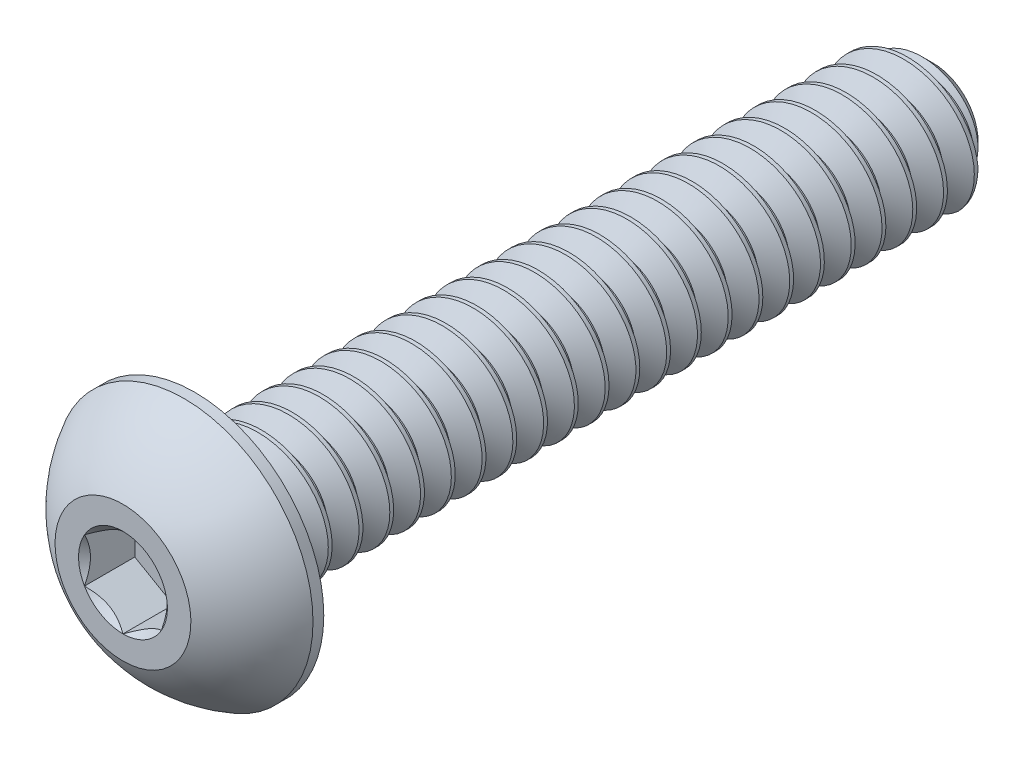
SolidWorks part; units mm, degrees
ref_plane "Front" through (0, 0, 0) normal (0, 0, 1) x (1, 0, 0)
ref_plane "Top" through (0, 0, 0) normal (0, 1, 0) x (1, 0, 0)
ref_plane "Right" through (0, 0, 0) normal (1, 0, 0) x (0, 0, -1)
sketch "Sketch1" plane through (0, 0, 0) normal (1, 0, 0) x (0, 0, -1)
  line L2 (1.8542, 1.7526) -> (20.9042, 1.7526)
  line L3 (20.9042, 1.7526) -> (20.9042, 0)
  line L4 (20.9042, 0) -> (1.8542, 0)
  line L6 (1.5761, 3.3274) -> (1.8542, 3.3274) construction
  line L7 (20.9042, 1.7526) -> (20.9042, -1.7526) construction
  line L8 (0, 0) -> (1.8542, 0) construction
  line L9 (1.8542, 3.3274) -> (1.8542, -3.3274) construction
  line L11 (1.8542, 1.7526) -> (1.8542, 0)
  line L13 (0, 0.9922) -> (0, -0.9922) construction
  line L14 (0, 0.9922) -> (0, 1.7526) construction
  arc A3 (0, 1.7526) -> (1.5761, 3.3274) centre (3.326, 0) cw construction
  dimension "D1" = 0.2781
revolve "Revolve1" add sketch "Sketch1" angle 360 mid plane about L4
sketch "Sketch3" plane through (0, 0, -20.9042) normal (0, 0, -1) x (-1, 0, 0)
  circle A0 centre (0, 0) radius 1.7526
curve "Helix/Spiral1" pitch 0.7937 height 19.8438 radius 1.7526 centre (0, 0, -20.9042) axis (0, 0, 1) start towards (0, 1, 0)
sketch "Sketch2" plane through (0, 0, 0) normal (1, 0, 0) x (0, 0, -1)
  line L0 (20.9042, 1.7526) -> (21.5987, 1.7526)
  line L1 (21.5987, 1.7526) -> (21.3011, 1.237)
  line L2 (21.3011, 1.237) -> (21.2019, 1.237)
  line L3 (21.2019, 1.237) -> (20.9042, 1.7526)
  line L4 (21.053, 1.4948) -> (21.4499, 1.4948) construction
  dimension "D1" = 60
  dimension "D2" = 0.0992
  dimension "D3" = 0.3969
chamfer "Chamfer1" distance 0.5953 angle 45 1 edges at (0, 1.7526, -20.9042)
sweep "Cut-Sweep1" cut profiles "Sketch2" path "Helix/Spiral1" align with end faces yes
sketch "Sketch7" plane through (0, 0, 0) normal (1, 0, 0) x (0, 0, -1)
  line L6 (1.5761, 3.3274) -> (1.8542, 3.3274) construction
  line L8 (0, 0) -> (1.8542, 0) construction
  line L11 (1.8542, 3.3274) -> (1.8542, -3.3274) construction
  line L12 (1.5761, 3.3274) -> (1.8542, 3.3274)
  line L13 (0, 0) -> (1.8542, 0)
  line L14 (0, 0.9922) -> (0, -0.9922) construction
  line L15 (1.8542, 3.3274) -> (1.8542, 0)
  line L16 (0, 1.7526) -> (0, 0)
  arc A2 (1.5761, 3.3274) -> (0, 1.7526) centre (3.326, 0) ccw construction
  arc A3 (1.5761, 3.3274) -> (0, 1.7526) centre (3.326, 0) ccw
revolve "Revolve2" add sketch "Sketch7" angle 360 mid plane about L13
sketch "Sketch5" plane through (0, 0, 0) normal (0, 0, 1) x (1, 0, 0)
  line L1 (0.9922, -0.5728) -> (0.9922, 0.5728)
  line L2 (0.9922, 0.5728) -> (0, 1.1457)
  line L3 (0, 1.1457) -> (-0.9922, 0.5728)
  line L4 (-0.9922, 0.5728) -> (-0.9922, -0.5728)
  line L5 (-0.9922, -0.5728) -> (0, -1.1457)
  line L6 (0, -1.1457) -> (0.9922, -0.5728)
  circle A0 centre (0, 0) radius 0.9922 construction
extrude "Cut-Extrude2" cut sketch "Sketch5" against normal blind 1.2979
sketch "Sketch6" plane through (0, 0, 0) normal (0, 0, 1) x (1, 0, 0)
  circle A0 centre (0, 0) radius 1.1457
extrude "Cut-Extrude3" cut sketch "Sketch6" against normal blind 1.2979 draft 45
sketch "Sketch9" [suppressed] plane through (0, 0, -1.4986) normal (0, 0, 1) x (1, 0, 0)
  circle A2 centre (0, 0) radius 1.4224
extrude "Boss-Extrude2" [suppressed] add sketch "Sketch9" against normal offset from surface (12.7 mm away) 31.75 up to face at (0, 1.1573, -20.9042)
sketch "Sketch10" plane through (0, 0, 0) normal (1, 0, 0) x (0, 0, -1)
  line L0 (20.9042, 1.7526) -> (20.9042, -1.7526) construction
  point P0 (19.7136, -1.7526)
  dimension "D1" = 1.1906
equation "\"D3@Helix/Spiral1\" = \"Lg@Sketch1\" + \"D4@Helix/Spiral1\""
equation "\"D2@Sketch2\" = \"D4@Helix/Spiral1\" * .125"
equation "\"D3@Sketch2\" = \"D4@Helix/Spiral1\" * .5"
equation "\"D1@Chamfer1\" = \"D4@Helix/Spiral1\" * .75"
equation "\"D1@Cut-Extrude2\" = \"Head Ht@Sketch1\" * .7"
equation "\"D1@Sketch1\" = \"Head Ht@Sketch1\" * .15"
equation "\"D1@Sketch10\" = \"D4@Helix/Spiral1\" * 1.5"
equation "\"D1@Cut-Extrude3\" = \"D1@Cut-Extrude2\""
